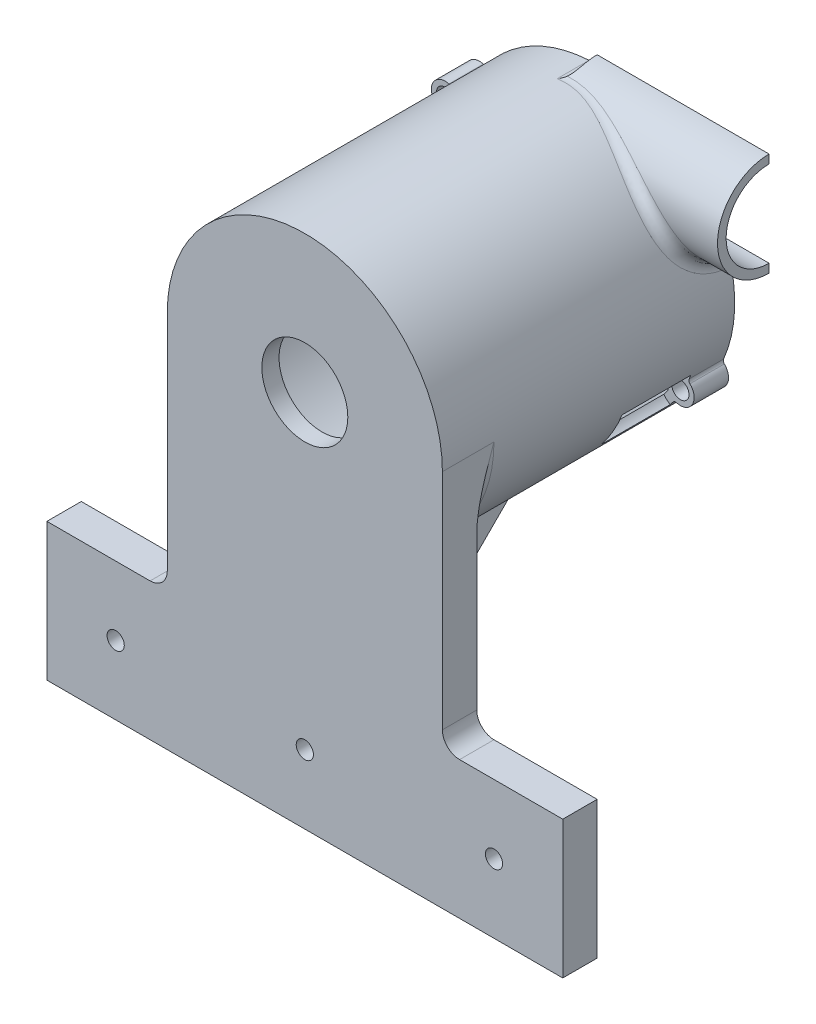
SolidWorks part; units mm, degrees
ref_plane "前视基准面" through (0, 0, 0) normal (0, 0, 1) x (1, 0, 0)
ref_plane "上视基准面" through (0, 0, 0) normal (0, 1, 0) x (1, 0, 0)
ref_plane "右视基准面" through (0, 0, 0) normal (1, 0, 0) x (0, 0, -1)
sketch "草图1" plane through (0, 0, 0) normal (0, 0, 1) x (1, 0, 0)
  circle A0 centre (0, 0) radius 37.5
  circle A1 centre (0, 0) radius 40
  dimension "D1" = 80
  dimension "D2" = 75
extrude "凸台-拉伸1" add sketch "草图1" along normal blind 70
sketch "草图2" plane through (0, 0, 0) normal (0, 0, -1) x (-1, 0, 0)
  line L0 (0, 0) -> (0, -12.7631) construction
  line L1 (0, 0) -> (0, -39.5) construction
  line L2 (0, 0) -> (-34.208, -19.75) construction
  line L3 (0, 0) -> (34.208, -19.75) construction
  line L4 (0, 0) -> (34.208, 19.75) construction
  circle A0 centre (0, 0) radius 39.5 construction
  circle A6 centre (34.208, -19.75) radius 4
  circle A7 centre (34.208, -19.75) radius 2.5
  circle A8 centre (0, -39.5) radius 4
  circle A9 centre (0, -39.5) radius 2.5
  circle A10 centre (-34.208, -19.75) radius 4
  circle A11 centre (-34.208, -19.75) radius 2.5
  circle A14 centre (34.208, 19.75) radius 2.5
  circle A15 centre (34.208, 19.75) radius 4
  dimension "D1" = 79
  dimension "D2" = 60
  dimension "D3" = 60
  dimension "D4" = 60
extrude "凸台-拉伸2" add sketch "草图2" against normal blind 10
sketch "草图3" plane through (0, 0, 0) normal (0, 0, -1) x (-1, 0, 0)
  line L0 (0, 0) -> (0, -11.2482) construction
  circle A1 centre (-34.208, -19.75) radius 2.5
  circle A2 centre (0, -39.5) radius 2.5
  circle A3 centre (34.208, -19.75) radius 2.5
  circle A4 centre (34.208, 19.75) radius 2.5
  point P0 (34.208, 19.75)
  point P1 (0, 0)
  point P2 (0, 0)
  point P18 (0, 0)
extrude "切除-拉伸1" cut sketch "草图3" against normal blind 10
sketch "草图5" plane through (0, 0, 10) normal (0, 0, -1) x (-1, 0, 0)
  line L0 (0, 0) -> (0, 15.5296) construction
  circle A1 centre (-34.208, -19.75) radius 6
  circle A2 centre (0, -39.5) radius 6
  circle A3 centre (34.208, -19.75) radius 6
  circle A4 centre (34.208, 19.75) radius 6
  point P0 (34.208, 19.75)
  point P1 (0, 0)
  dimension "D1" = 12
extrude "切除-拉伸3" cut sketch "草图5" against normal blind 20
sketch "草图6" plane through (0, 0, 0) normal (1, 0, 0) x (0, 0, -1)
  line L0 (0, -16.446) -> (0, 16.446) construction
  line L1 (0, 40) -> (-70, 40) construction
  line L2 (0, 42.5) -> (0, 40)
  line L3 (0, 15) -> (0, 12.5)
  arc A0 (0, 40) -> (0, 15) centre (0, 27.5) ccw
  arc A1 (0, 42.5) -> (0, 12.5) centre (0, 27.5) ccw
  dimension "D1" = 25
  dimension "D2" = 30
extrude "凸台-拉伸3" add sketch "草图6" along normal blind 50
sketch "草图7" plane through (50, 0, 0) normal (1, 0, 0) x (0, 0, -1)
  line L0 (0, 15) -> (0, 40) construction
  circle A0 centre (0, 27.5) radius 12.5
extrude "切除-拉伸4" cut sketch "草图7" against normal blind 50
sketch "草图9" plane through (0, 0, 0) normal (0, 0, -1) x (-1, 0, 0)
  line L0 (0, 37.5) -> (0, 6.3585)
  line L1 (0, 15) -> (0, 37.5) construction
  line L2 (0, 6.3585) -> (-35.3553, 12.5)
  arc A1 (30.6585, 21.5942) -> (0, 37.5) centre (0, 0) ccw construction
  arc A2 (0, 37.5) -> (-35.3553, 12.5) centre (0, 0) ccw
extrude "切除-拉伸6" cut sketch "草图9" against normal blind 20.5
chamfer "倒角2" distance 2.5 angle 45 1 edges at (0, 37.5, 3.75)
fillet "圆角4" radius 2.5 1 edges at (0, 40, 4.1458)
fillet "圆角6" radius 1 8 edges at (32.474, -23.3546, 5) (36.4627, -16.446, 5) (3.9887, -39.8006, 5) (-3.9887, -39.8006, 5) (-36.4627, 16.446, 5) (-32.474, -23.3546, 5) (-36.4627, -16.446, 5) (-32.474, 23.3546, 5)
fillet "圆角7" radius 3 1 edges at (27.3574, 29.1818, 14.9054)
sketch "草图10" plane through (0, 0, 70) normal (0, 0, 1) x (1, 0, 0)
  circle A0 centre (0, 0) radius 37.5
  circle A1 centre (0, 0) radius 40
extrude "凸台-拉伸4" add sketch "草图10" along normal blind 10
sketch "草图11" plane through (0, 0, 80) normal (0, 0, 1) x (1, 0, 0)
  circle A0 centre (0, 0) radius 40
extrude "凸台-拉伸5" add sketch "草图11" along normal blind 5
sketch "草图12" plane through (0, 0, 85) normal (0, 0, 1) x (1, 0, 0)
  circle A0 centre (0, 0) radius 12.5
  dimension "D1" = 25
extrude "切除-拉伸7" cut sketch "草图12" against normal blind 5
sketch "草图13" plane through (0, 0, 85) normal (0, 0, 1) x (1, 0, 0)
  line L0 (-40, 0) -> (40, 0)
  line L1 (40, 0) -> (40, -70)
  line L3 (0, 0) -> (0, 26.2579) construction
  line L4 (-40, 0) -> (-40, -70)
  line L5 (40, -70) -> (75, -70)
  line L6 (-75, -110) -> (75, -110)
  line L7 (-75, -110) -> (-75, -70)
  line L8 (-75, -70) -> (-40, -70)
  line L9 (75, -110) -> (75, -70)
  line L10 (0, -70) -> (0, -110) construction
  point P7 (0, -90)
  point P8 (0, -90)
  point P12 (0, 0)
  dimension "D2" = 80
  dimension "D3" = 150
  dimension "D4" = 40
extrude "凸台-拉伸6" add sketch "草图13" against normal blind 10
sketch "草图14" plane through (0, 0, 85) normal (0, 0, 1) x (1, 0, 0)
  line L0 (12.5, 0) -> (-12.5, 0) construction
  circle A0 centre (0, 0) radius 12.5
extrude "切除-拉伸8" cut sketch "草图14" against normal blind 20
sketch "草图15" plane through (0, 0, 75) normal (0, 0, -1) x (-1, 0, 0)
  circle A0 centre (0, 0) radius 37.5
extrude "切除-拉伸9" cut sketch "草图15" against normal up to surface (5 mm away) up to face at (0, 12.5, 80)
ref_plane "基准面1" through (20, 0, 0) normal (1, 0, 0) x (0, 0, -1)
sketch "草图16" plane through (20, 0, 0) normal (1, 0, 0) x (0, 0, -1)
  line L0 (-45, -30.6254) -> (-75, -60.6254)
  line L1 (-75, -70) -> (-75, 0) construction
  line L3 (-75, -60.6254) -> (-75, -30.6254)
  line L5 (-45, -30.6254) -> (-75, -30.6254)
  point P2 (0, 0)
  dimension "D1" = 45
  dimension "D2" = 30
extrude "凸台-拉伸7" add sketch "草图16" along normal mid plane 5
mirror "镜向1" about plane through (0, 0, 0) normal (1, 0, 0) of "凸台-拉伸7"
sketch "草图17" plane through (0, 0, 80) normal (0, 0, -1) x (-1, 0, 0)
  circle A0 centre (0, 0) radius 37.5
extrude "切除-拉伸10" cut sketch "草图17" along normal blind 43
fillet "圆角8" radius 5 2 edges at (-40, -70, 80) (40, -70, 80)
fillet "圆角9" radius 5 3 edges at (35.3553, -18.7083, 75) (0, -40, 75) (-35.3553, -18.7083, 75)
sketch "草图18" plane through (0, 0, 85) normal (0, 0, 1) x (1, 0, 0)
  line L0 (0, 0) -> (0, -55.7416) construction
  line L1 (-75, -70) -> (-75, -110) construction
  circle A0 centre (-55, -90) radius 2.5
  circle A2 centre (55, -90) radius 2.5
  circle A3 centre (0, -90) radius 2.5
  point P6 (-75, -90)
  dimension "D1" = 5
  dimension "D3" = 5
  dimension "D2" = 20
extrude "切除-拉伸11" cut sketch "草图18" against normal blind 43
